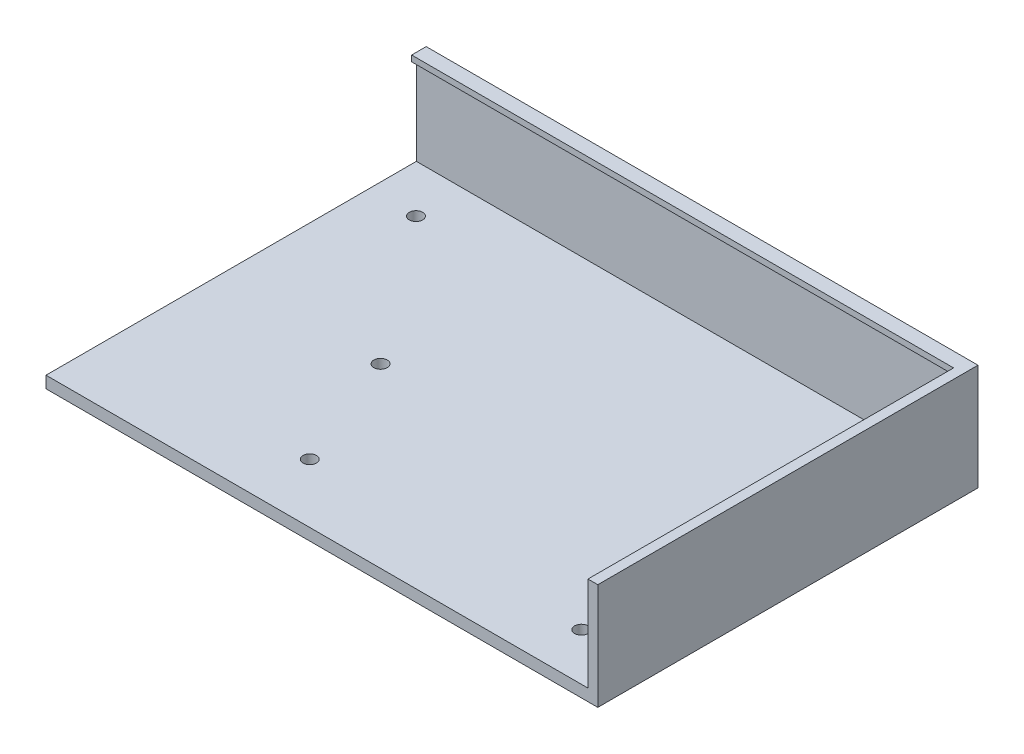
SolidWorks part; units mm, degrees
ref_plane "Front Plane" through (0, 0, 0) normal (0, 0, 1) x (1, 0, 0)
ref_plane "Top Plane" through (0, 0, 0) normal (0, 1, 0) x (1, 0, 0)
ref_plane "Right Plane" through (0, 0, 0) normal (1, 0, 0) x (0, 0, -1)
sketch "Sketch1" plane through (0, 0, 0) normal (0, 1, 0) x (1, 0, 0)
  line L1 (-140.2, -96.6) -> (140.2, -96.6)
  line L2 (-140.2, -96.6) -> (-140.2, 96.6)
  line L3 (-140.2, 96.6) -> (140.2, 96.6)
  line L4 (140.2, -96.6) -> (140.2, 96.6)
  line L5 (-140.2, -96.6) -> (140.2, 96.6) construction
  line L6 (-140.2, 96.6) -> (140.2, -96.6) construction
  dimension "D1" = 280.4
  dimension "D2" = 193.2
extrude "Shell Block" add sketch "Sketch1" along normal blind 27
ref_plane "Shell Front" through (0, 27, 0) normal (0, 1, 0) x (1, 0, 0)
sketch "Sketch2" plane through (0, 27, 0) normal (0, 1, 0) x (1, 0, 0)
  line L1 (-137.7, -92.9) -> (137.7, -92.9)
  line L2 (-137.7, -92.9) -> (-137.7, 92.9)
  line L3 (-137.7, 92.9) -> (137.7, 92.9)
  line L4 (137.7, -92.9) -> (137.7, 92.9)
  line L5 (-137.7, -92.9) -> (137.7, 92.9) construction
  line L6 (-137.7, 92.9) -> (137.7, -92.9) construction
  dimension "D1" = 275.4
  dimension "D2" = 185.8
extrude "Front Opening" cut sketch "Sketch2" against normal blind 1.5
ref_plane "Under Lip" through (0, 25.5, 0) normal (0, 1, 0) x (1, 0, 0)
sketch "Sketch3" plane through (0, 25.5, 0) normal (0, 1, 0) x (1, 0, 0)
  line L1 (-137.7, -94.1) -> (137.7, -94.1)
  line L2 (-137.7, -94.1) -> (-137.7, 94.1)
  line L3 (-137.7, 94.1) -> (137.7, 94.1)
  line L4 (137.7, -94.1) -> (137.7, 94.1)
  line L5 (-137.7, -94.1) -> (137.7, 94.1) construction
  line L6 (-137.7, 94.1) -> (137.7, -94.1) construction
  dimension "D1" = 275.4
  dimension "D2" = 188.2
extrude "Display Pocket" cut sketch "Sketch3" against normal blind 22.5
ref_plane "Back Inner" through (0, 3, 0) normal (0, 1, 0) x (1, 0, 0)
sketch "Sketch4" plane through (0, 3, 0) normal (0, 1, 0) x (1, 0, 0)
  line L1 (-69, 28) -> (-66, 28)
  line L2 (-69, 28) -> (-69, 84)
  line L3 (-69, 84) -> (-66, 84)
  line L4 (-66, 28) -> (-66, 84)
  line L6 (-69, -84) -> (-66, -84)
  line L7 (-69, -84) -> (-69, -28)
  line L8 (-69, -28) -> (-66, -28)
  line L9 (-66, -84) -> (-66, -28)
  line L11 (-77, 28) -> (-74, 28)
  line L12 (-77, 28) -> (-77, 84)
  line L13 (-77, 84) -> (-74, 84)
  line L14 (-74, 28) -> (-74, 84)
  line L16 (-77, -84) -> (-74, -84)
  line L17 (-77, -84) -> (-77, -28)
  line L18 (-77, -28) -> (-74, -28)
  line L19 (-74, -84) -> (-74, -28)
  line L21 (-85, 28) -> (-82, 28)
  line L22 (-85, 28) -> (-85, 84)
  line L23 (-85, 84) -> (-82, 84)
  line L24 (-82, 28) -> (-82, 84)
  line L26 (-85, -84) -> (-82, -84)
  line L27 (-85, -84) -> (-85, -28)
  line L28 (-85, -28) -> (-82, -28)
  line L29 (-82, -84) -> (-82, -28)
  line L31 (-93, 28) -> (-90, 28)
  line L32 (-93, 28) -> (-93, 84)
  line L33 (-93, 84) -> (-90, 84)
  line L34 (-90, 28) -> (-90, 84)
  line L36 (-93, -84) -> (-90, -84)
  line L37 (-93, -84) -> (-93, -28)
  line L38 (-93, -28) -> (-90, -28)
  line L39 (-90, -84) -> (-90, -28)
  line L41 (-101, 28) -> (-98, 28)
  line L42 (-101, 28) -> (-101, 84)
  line L43 (-101, 84) -> (-98, 84)
  line L44 (-98, 28) -> (-98, 84)
  line L46 (-101, -84) -> (-98, -84)
  line L47 (-101, -84) -> (-101, -28)
  line L48 (-101, -28) -> (-98, -28)
  line L49 (-98, -84) -> (-98, -28)
  line L51 (-109, 28) -> (-106, 28)
  line L52 (-109, 28) -> (-109, 84)
  line L53 (-109, 84) -> (-106, 84)
  line L54 (-106, 28) -> (-106, 84)
  line L56 (-109, -84) -> (-106, -84)
  line L57 (-109, -84) -> (-109, -28)
  line L58 (-109, -28) -> (-106, -28)
  line L59 (-106, -84) -> (-106, -28)
  line L61 (-117, 28) -> (-114, 28)
  line L62 (-117, 28) -> (-117, 84)
  line L63 (-117, 84) -> (-114, 84)
  line L64 (-114, 28) -> (-114, 84)
  line L66 (-117, -84) -> (-114, -84)
  line L67 (-117, -84) -> (-117, -28)
  line L68 (-117, -28) -> (-114, -28)
  line L69 (-114, -84) -> (-114, -28)
  line L71 (-125, 28) -> (-122, 28)
  line L72 (-125, 28) -> (-125, 84)
  line L73 (-125, 84) -> (-122, 84)
  line L74 (-122, 28) -> (-122, 84)
  line L76 (-125, -84) -> (-122, -84)
  line L77 (-125, -84) -> (-125, -28)
  line L78 (-125, -28) -> (-122, -28)
  line L79 (-122, -84) -> (-122, -28)
extrude "Vent Slots" cut sketch "Sketch4" against normal blind 4
sketch "Sketch5" plane through (0, 0, 0) normal (1, 0, 0) x (0, 0, -1)
  line L1 (-35, 5) -> (35, 5)
  line L2 (-35, 5) -> (-35, 21)
  line L3 (-35, 21) -> (35, 21)
  line L4 (35, 5) -> (35, 21)
extrude "Cable Exit (-X short side)" cut sketch "Sketch5" against normal blind 141.2
sketch "Sketch6" plane through (0, 3, 0) normal (0, 1, 0) x (1, 0, 0)
  circle A0 centre (-40, -45) radius 1.7
  circle A1 centre (-40, 45) radius 1.7
  circle A2 centre (40, -45) radius 1.7
  circle A3 centre (40, 45) radius 1.7
  circle A4 centre (-52, -15) radius 1.7
  circle A5 centre (-52, 15) radius 1.7
  circle A6 centre (52, -15) radius 1.7
  circle A7 centre (52, 15) radius 1.7
  circle A8 centre (-12, -82) radius 1.7
  circle A9 centre (-12, 82) radius 1.7
  circle A10 centre (12, -82) radius 1.7
  circle A11 centre (12, 82) radius 1.7
  circle A12 centre (-124, -12) radius 1.7
  circle A13 centre (-124, 12) radius 1.7
  circle A14 centre (124, -12) radius 1.7
  circle A15 centre (124, 12) radius 1.7
extrude "Bolt Holes" cut sketch "Sketch6" against normal blind 4
sketch "Sketch7" plane through (0, 0, 0) normal (0, 1, 0) x (1, 0, 0)
  line L1 (-200, -200) -> (0, -200)
  line L2 (-200, -200) -> (-200, 200)
  line L3 (-200, 200) -> (0, 200)
  line L4 (0, -200) -> (0, 200)
extrude "Keep one half (X)" cut sketch "Sketch7" against normal through all and the other way through all
sketch "Sketch8" plane through (0, 0, 0) normal (0, 1, 0) x (1, 0, 0)
  line L1 (-200, 0) -> (200, 0)
  line L2 (-200, 0) -> (-200, -200)
  line L3 (-200, -200) -> (200, -200)
  line L4 (200, 0) -> (200, -200)
extrude "Keep one quarter (Z)" cut sketch "Sketch8" against normal through all and the other way through all
equation "\"DispL\"= 274.2"
equation "\"DispW\"= 187.0"
equation "\"DispT\"= 20.0"
equation "\"Clr\"= 0.6"
equation "\"Wall\"= 2.5"
equation "\"BackT\"= 3.0"
equation "\"CableRoom\"= 4.0"
equation "\"LipW\"= 1.2"
equation "\"LipT\"= 1.5"
equation "\"CableW\"= 70.0"
equation "\"CableH\"= 16.0"
equation "\"BoltD\"= 3.4"
equation "\"ShellL\"= \"DispL\" + 2 * \"Clr\" + 2 * \"Wall\""
equation "\"ShellW\"= \"DispW\" + 2 * \"Clr\" + 2 * \"Wall\""
equation "\"ShellH\"= \"BackT\" + \"DispT\" + \"CableRoom\""
equation "\"D1@Sketch1\" = \"ShellL\""
equation "\"D2@Sketch1\" = \"ShellW\""
equation "\"D1@Shell Block\" = \"ShellH\""
equation "\"D1@Shell Front\" = \"ShellH\""
equation "\"D1@Sketch2\" = \"DispL\" + 2 * \"Clr\""
equation "\"D2@Sketch2\" = \"DispW\" + 2 * \"Clr\" - 2 * \"LipW\""
equation "\"D1@Front Opening\" = \"LipT\""
equation "\"D1@Under Lip\" = \"ShellH\" - \"LipT\""
equation "\"D1@Sketch3\" = \"DispL\" + 2 * \"Clr\""
equation "\"D2@Sketch3\" = \"DispW\" + 2 * \"Clr\""
equation "\"D1@Display Pocket\" = \"ShellH\" - \"LipT\" - \"BackT\""
equation "\"D1@Back Inner\" = \"BackT\""
